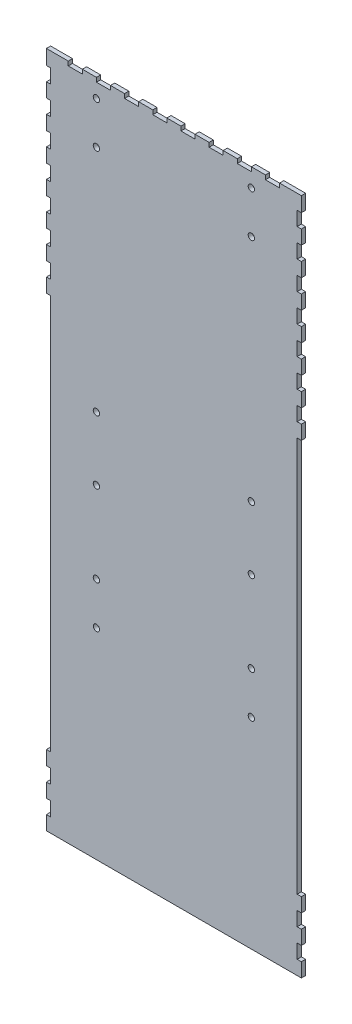
SolidWorks part; units mm, degrees
ref_plane "Front Plane" through (0, 0, 0) normal (0, 0, 1) x (1, 0, 0)
ref_plane "Top Plane" through (0, 0, 0) normal (0, 1, 0) x (1, 0, 0)
ref_plane "Right Plane" through (0, 0, 0) normal (1, 0, 0) x (0, 0, -1)
sketch "Sketch1" plane through (0, 0, 0) normal (0, 0, 1) x (1, 0, 0)
  line L2 (3, 408) -> (-12.5, 408)
  line L3 (-178, 408) -> (-178, 397.5)
  line L4 (-175, 0) -> (0, 0)
  line L5 (0, 0) -> (0, 405)
  line L6 (0, 405) -> (-175, 405)
  line L7 (-175, 405) -> (-175, 0)
  line L8 (-175, 0) -> (0, 0) construction
  line L10 (0, 405) -> (-175, 405) construction
  line L11 (-175, 405) -> (-175, 0) construction
  line L12 (-178, 397.5) -> (-175, 397.5)
  line L13 (-175, 397.5) -> (-175, 387.5)
  line L14 (-175, 387.5) -> (-178, 387.5)
  line L15 (-178, 387.5) -> (-178, 377.5)
  line L16 (-178, 408) -> (-178, -3) construction
  line L17 (-87.5, 408) -> (-87.5, -3) construction
  line L18 (-178, 377.5) -> (-175, 377.5)
  line L19 (-175, 377.5) -> (-175, 367.5)
  line L20 (-175, 367.5) -> (-178, 367.5)
  line L21 (-178, 357.5) -> (-175, 357.5)
  line L22 (-175, 357.5) -> (-175, 347.5)
  line L23 (-175, 347.5) -> (-178, 347.5)
  line L24 (-178, 337.5) -> (-175, 337.5)
  line L25 (-175, 337.5) -> (-175, 327.5)
  line L26 (-175, 327.5) -> (-178, 327.5)
  line L27 (-178, 317.5) -> (-175, 317.5)
  line L28 (-175, 317.5) -> (-175, 307.5)
  line L29 (-175, 307.5) -> (-178, 307.5)
  line L30 (-178, 297.5) -> (-175, 297.5)
  line L31 (-175, 297.5) -> (-175, 287.5)
  line L32 (-175, 287.5) -> (-178, 287.5)
  line L33 (-178, 277.5) -> (-175, 277.5)
  line L34 (-175, 277.5) -> (-175, 267.5)
  line L35 (-175, 267.5) -> (-178, 267.5)
  line L75 (-178, 367.5) -> (-178, 357.5)
  line L76 (-178, 347.5) -> (-178, 337.5)
  line L77 (-178, 327.5) -> (-178, 317.5)
  line L78 (-178, 307.5) -> (-178, 297.5)
  line L79 (-178, 287.5) -> (-178, 277.5)
  line L94 (3, -3) -> (3, 408) construction
  line L95 (0, 0) -> (0, 405) construction
  line L96 (0, 405) -> (0, 0) construction
  line L111 (3, 287.5) -> (3, 277.5)
  line L112 (3, 307.5) -> (3, 297.5)
  line L113 (3, 327.5) -> (3, 317.5)
  line L114 (3, 347.5) -> (3, 337.5)
  line L115 (3, 367.5) -> (3, 357.5)
  line L155 (0, 267.5) -> (3, 267.5)
  line L156 (0, 277.5) -> (0, 267.5)
  line L157 (3, 277.5) -> (0, 277.5)
  line L158 (0, 287.5) -> (3, 287.5)
  line L159 (0, 297.5) -> (0, 287.5)
  line L160 (3, 297.5) -> (0, 297.5)
  line L161 (0, 307.5) -> (3, 307.5)
  line L162 (0, 317.5) -> (0, 307.5)
  line L163 (3, 317.5) -> (0, 317.5)
  line L164 (0, 327.5) -> (3, 327.5)
  line L165 (0, 337.5) -> (0, 327.5)
  line L166 (3, 337.5) -> (0, 337.5)
  line L167 (0, 347.5) -> (3, 347.5)
  line L168 (0, 357.5) -> (0, 347.5)
  line L169 (3, 357.5) -> (0, 357.5)
  line L170 (0, 367.5) -> (3, 367.5)
  line L171 (0, 377.5) -> (0, 367.5)
  line L172 (3, 377.5) -> (0, 377.5)
  line L173 (3, 387.5) -> (3, 377.5)
  line L174 (0, 387.5) -> (3, 387.5)
  line L175 (0, 397.5) -> (0, 387.5)
  line L176 (3, 397.5) -> (0, 397.5)
  line L177 (3, 408) -> (3, 397.5)
  line L178 (-162.5, 408) -> (-162.5, 405)
  line L179 (-162.5, 405) -> (-152.5, 405)
  line L180 (-152.5, 405) -> (-152.5, 408)
  line L181 (-162.5, 408) -> (-178, 408)
  line L182 (3, 408) -> (-178, 408) construction
  line L183 (-142.5, 408) -> (-142.5, 405)
  line L184 (-132.5, 405) -> (-132.5, 408)
  line L185 (-142.5, 405) -> (-132.5, 405)
  line L186 (-122.5, 408) -> (-122.5, 405)
  line L187 (-112.5, 405) -> (-112.5, 408)
  line L188 (-122.5, 405) -> (-112.5, 405)
  line L189 (-102.5, 408) -> (-102.5, 405)
  line L190 (-92.5, 405) -> (-92.5, 408)
  line L191 (-102.5, 405) -> (-92.5, 405)
  line L192 (-82.5, 408) -> (-82.5, 405)
  line L193 (-72.5, 405) -> (-72.5, 408)
  line L194 (-82.5, 405) -> (-72.5, 405)
  line L195 (-62.5, 408) -> (-62.5, 405)
  line L196 (-52.5, 405) -> (-52.5, 408)
  line L197 (-62.5, 405) -> (-52.5, 405)
  line L198 (-42.5, 408) -> (-42.5, 405)
  line L199 (-32.5, 405) -> (-32.5, 408)
  line L200 (-42.5, 405) -> (-32.5, 405)
  line L201 (-22.5, 408) -> (-22.5, 405)
  line L202 (-12.5, 405) -> (-12.5, 408)
  line L203 (-22.5, 405) -> (-12.5, 405)
  line L204 (-142.5, 408) -> (-152.5, 408)
  line L205 (-122.5, 408) -> (-132.5, 408)
  line L206 (-102.5, 408) -> (-112.5, 408)
  line L207 (-82.5, 408) -> (-92.5, 408)
  line L208 (-62.5, 408) -> (-72.5, 408)
  line L209 (-42.5, 408) -> (-52.5, 408)
  line L210 (-22.5, 408) -> (-32.5, 408)
  line L211 (-178, 262.5) -> (-192.1885, 262.5) construction
  line L213 (-175, 247.5) -> (-178, 247.5) [skipped]
  line L214 (-178, 237.5) -> (-175, 237.5) [skipped]
  line L215 (-175, 237.5) -> (-175, 227.5) [skipped]
  line L216 (-175, 227.5) -> (-178, 227.5) [skipped]
  line L217 (-178, 217.5) -> (-175, 217.5) [skipped]
  line L218 (-175, 217.5) -> (-175, 207.5) [skipped]
  line L219 (-175, 207.5) -> (-178, 207.5) [skipped]
  line L220 (-178, 197.5) -> (-175, 197.5) [skipped]
  line L221 (-175, 197.5) -> (-175, 187.5) [skipped]
  line L222 (-175, 187.5) -> (-178, 187.5) [skipped]
  line L223 (-178, 177.5) -> (-175, 177.5) [skipped]
  line L224 (-175, 177.5) -> (-175, 167.5) [skipped]
  line L225 (-175, 167.5) -> (-178, 167.5) [skipped]
  line L226 (-178, 157.5) -> (-175, 157.5) [skipped]
  line L227 (-175, 157.5) -> (-175, 147.5) [skipped]
  line L228 (-175, 147.5) -> (-178, 147.5) [skipped]
  line L229 (-178, 137.5) -> (-175, 137.5) [skipped]
  line L230 (-175, 137.5) -> (-175, 127.5) [skipped]
  line L231 (-175, 127.5) -> (-178, 127.5) [skipped]
  line L232 (-178, 117.5) -> (-175, 117.5) [skipped]
  line L233 (-175, 117.5) -> (-175, 107.5) [skipped]
  line L234 (-175, 107.5) -> (-178, 107.5) [skipped]
  line L235 (-178, 97.5) -> (-175, 97.5) [skipped]
  line L236 (-175, 97.5) -> (-175, 87.5) [skipped]
  line L237 (-175, 87.5) -> (-178, 87.5) [skipped]
  line L238 (-178, 77.5) -> (-175, 77.5) [skipped]
  line L239 (-175, 77.5) -> (-175, 67.5) [skipped]
  line L240 (-175, 67.5) -> (-178, 67.5) [skipped]
  line L241 (-178, 57.5) -> (-175, 57.5) [skipped]
  line L242 (-175, 57.5) -> (-175, 47.5) [skipped]
  line L243 (-175, 47.5) -> (-178, 47.5) [skipped]
  line L244 (-178, 37.5) -> (-175, 37.5) [skipped]
  line L245 (-175, 37.5) -> (-175, 27.5) [skipped]
  line L246 (-175, 27.5) -> (-178, 27.5) [skipped]
  line L247 (-178, 17.5) -> (-175, 17.5) [skipped]
  line L248 (-175, 17.5) -> (-175, 7.5) [skipped]
  line L249 (-175, 7.5) -> (-178, 7.5) [skipped]
  line L250 (-175, 257.5) -> (-175, 247.5) [skipped]
  line L251 (-178, 257.5) -> (-175, 257.5) [skipped]
  line L254 (-178, -73) -> (3, -73)
  line L256 (-178, -3) -> (3, -3) construction
  line L257 (-178, -3) -> (3, -3) construction
  line L258 (-178, 267.5) -> (-178, 257.5)
  line L259 (-178, 257.5) -> (-175, 257.5)
  line L260 (3, 267.5) -> (3, 257.5)
  line L261 (3, 257.5) -> (0, 257.5)
  line L262 (-175, 257.5) -> (-175, 0)
  line L267 (0, 0) -> (0, 257.5)
  line L269 (-178, -23) -> (-175, -23)
  line L270 (-175, -23) -> (-175, 0)
  line L272 (3, -23) -> (0, -23)
  line L273 (0, -23) -> (0, 0)
  line L274 (-178, -33) -> (-175, -33)
  line L275 (-175, -33) -> (-175, -43)
  line L276 (-175, -43) -> (-178, -43)
  line L277 (-178, -43) -> (-178, -53)
  line L278 (-178, -53) -> (-175, -53)
  line L279 (-175, -53) -> (-175, -63)
  line L280 (-175, -63) -> (-178, -63)
  line L281 (-178, -33) -> (-178, -23)
  line L282 (-178, -73) -> (-178, -63)
  line L283 (3, -33) -> (0, -33)
  line L284 (0, -33) -> (0, -43)
  line L285 (0, -43) -> (3, -43)
  line L286 (3, -43) -> (3, -53)
  line L287 (3, -53) -> (0, -53)
  line L288 (0, -53) -> (0, -63)
  line L289 (0, -63) -> (3, -63)
  line L290 (3, -33) -> (3, -23)
  line L291 (3, -73) -> (3, -63)
  dimension "D3" = 10.5
  dimension "D4" = 10
  dimension "D6" = 10
  dimension "D7" = 10
  dimension "D8" = 15.5
  dimension "D10" = 10
  dimension "D11" = 481
  dimension "D12" = 10
  dimension "D13" = 50
  dimension "D14" = 50
  dimension "D15" = 3
  dimension "D16" = 3
  dimension "D17" = 3
  dimension "D18" = 10
  dimension "D19" = 10
  dimension "D20" = 10
  dimension "D21" = 10
  dimension "D22" = 10
  dimension "D23" = 10
  dimension "D24" = 10
  dimension "D25" = 10
  dimension "D26" = 10
  dimension "D27" = 10
  dimension "D28" = 10
  dimension "D1" = 0
  dimension "D2" = 3
  dimension "D5" = 20
  dimension "D9" = 8
extrude "Boss-Extrude1" add sketch "Sketch1" along normal blind 3
sketch "Sketch2" plane through (0, 0, 3) normal (0, 0, 1) x (1, 0, 0)
  line L116 (-175, 257.5) -> (-175, -23)
  line L117 (-175, -23) -> (-178, -23)
  line L118 (-178, -23) -> (-178, -33)
  line L119 (-178, -33) -> (-175, -33)
  line L120 (-175, -33) -> (-175, -43)
  line L121 (-175, -43) -> (-178, -43)
  line L122 (-178, -43) -> (-178, -53)
  line L123 (-178, -53) -> (-175, -53)
  line L124 (-175, -53) -> (-175, -63)
  line L125 (-175, -63) -> (-178, -63)
  line L126 (-178, -63) -> (-178, -73)
  line L127 (-178, -73) -> (3, -73)
  line L128 (3, -73) -> (3, -63)
  line L129 (3, -63) -> (0, -63)
  line L130 (0, -63) -> (0, -53)
  line L131 (0, -53) -> (3, -53)
  line L132 (3, -53) -> (3, -43)
  line L133 (3, -43) -> (0, -43)
  line L134 (0, -43) -> (0, -33)
  line L135 (0, -33) -> (3, -33)
  line L136 (3, -33) -> (3, -23)
  line L137 (3, -23) -> (0, -23)
  line L138 (0, -23) -> (0, 257.5)
  line L139 (0, 257.5) -> (3, 257.5)
  line L140 (3, 257.5) -> (3, 267.5)
  line L141 (3, 267.5) -> (0, 267.5)
  line L142 (0, 267.5) -> (0, 277.5)
  line L143 (0, 277.5) -> (3, 277.5)
  line L144 (3, 277.5) -> (3, 287.5)
  line L145 (3, 287.5) -> (0, 287.5)
  line L146 (0, 287.5) -> (0, 297.5)
  line L147 (0, 297.5) -> (3, 297.5)
  line L148 (3, 297.5) -> (3, 307.5)
  line L149 (3, 307.5) -> (0, 307.5)
  line L150 (0, 307.5) -> (0, 317.5)
  line L151 (0, 317.5) -> (3, 317.5)
  line L152 (3, 317.5) -> (3, 327.5)
  line L153 (3, 327.5) -> (0, 327.5)
  line L154 (0, 327.5) -> (0, 337.5)
  line L155 (0, 337.5) -> (3, 337.5)
  line L156 (3, 337.5) -> (3, 347.5)
  line L157 (3, 347.5) -> (0, 347.5)
  line L158 (0, 347.5) -> (0, 357.5)
  line L159 (0, 357.5) -> (3, 357.5)
  line L160 (3, 357.5) -> (3, 367.5)
  line L161 (3, 367.5) -> (0, 367.5)
  line L162 (0, 367.5) -> (0, 377.5)
  line L163 (0, 377.5) -> (3, 377.5)
  line L164 (3, 377.5) -> (3, 387.5)
  line L165 (3, 387.5) -> (0, 387.5)
  line L166 (0, 387.5) -> (0, 397.5)
  line L167 (0, 397.5) -> (3, 397.5)
  line L168 (3, 397.5) -> (3, 408)
  line L169 (3, 408) -> (-12.5, 408)
  line L170 (-12.5, 408) -> (-12.5, 405)
  line L171 (-12.5, 405) -> (-22.5, 405)
  line L172 (-22.5, 405) -> (-22.5, 408)
  line L173 (-22.5, 408) -> (-32.5, 408)
  line L174 (-32.5, 408) -> (-32.5, 405)
  line L175 (-32.5, 405) -> (-42.5, 405)
  line L176 (-42.5, 405) -> (-42.5, 408)
  line L177 (-42.5, 408) -> (-52.5, 408)
  line L178 (-52.5, 408) -> (-52.5, 405)
  line L179 (-52.5, 405) -> (-62.5, 405)
  line L180 (-62.5, 405) -> (-62.5, 408)
  line L181 (-62.5, 408) -> (-72.5, 408)
  line L182 (-72.5, 408) -> (-72.5, 405)
  line L183 (-72.5, 405) -> (-82.5, 405)
  line L184 (-82.5, 405) -> (-82.5, 408)
  line L185 (-82.5, 408) -> (-92.5, 408)
  line L186 (-92.5, 408) -> (-92.5, 405)
  line L187 (-92.5, 405) -> (-102.5, 405)
  line L188 (-102.5, 405) -> (-102.5, 408)
  line L189 (-102.5, 408) -> (-112.5, 408)
  line L190 (-112.5, 408) -> (-112.5, 405)
  line L191 (-112.5, 405) -> (-122.5, 405)
  line L192 (-122.5, 405) -> (-122.5, 408)
  line L193 (-122.5, 408) -> (-132.5, 408)
  line L194 (-132.5, 408) -> (-132.5, 405)
  line L195 (-132.5, 405) -> (-142.5, 405)
  line L196 (-142.5, 405) -> (-142.5, 408)
  line L197 (-142.5, 408) -> (-152.5, 408)
  line L198 (-152.5, 408) -> (-152.5, 405)
  line L199 (-152.5, 405) -> (-162.5, 405)
  line L200 (-162.5, 405) -> (-162.5, 408)
  line L201 (-162.5, 408) -> (-178, 408)
  line L202 (-178, 408) -> (-178, 397.5)
  line L203 (-178, 397.5) -> (-175, 397.5)
  line L204 (-175, 397.5) -> (-175, 387.5)
  line L205 (-175, 387.5) -> (-178, 387.5)
  line L206 (-178, 387.5) -> (-178, 377.5)
  line L207 (-178, 377.5) -> (-175, 377.5)
  line L208 (-175, 377.5) -> (-175, 367.5)
  line L209 (-175, 367.5) -> (-178, 367.5)
  line L210 (-178, 367.5) -> (-178, 357.5)
  line L211 (-178, 357.5) -> (-175, 357.5)
  line L212 (-175, 357.5) -> (-175, 347.5)
  line L213 (-175, 347.5) -> (-178, 347.5)
  line L214 (-178, 347.5) -> (-178, 337.5)
  line L215 (-178, 337.5) -> (-175, 337.5)
  line L216 (-175, 337.5) -> (-175, 327.5)
  line L217 (-175, 327.5) -> (-178, 327.5)
  line L218 (-178, 327.5) -> (-178, 317.5)
  line L219 (-178, 317.5) -> (-175, 317.5)
  line L220 (-175, 317.5) -> (-175, 307.5)
  line L221 (-175, 307.5) -> (-178, 307.5)
  line L222 (-178, 307.5) -> (-178, 297.5)
  line L223 (-178, 297.5) -> (-175, 297.5)
  line L224 (-175, 297.5) -> (-175, 287.5)
  line L225 (-175, 287.5) -> (-178, 287.5)
  line L226 (-178, 287.5) -> (-178, 277.5)
  line L227 (-178, 277.5) -> (-175, 277.5)
  line L228 (-175, 277.5) -> (-175, 267.5)
  line L229 (-175, 267.5) -> (-178, 267.5)
  line L230 (-178, 267.5) -> (-178, 257.5)
  line L231 (-178, 257.5) -> (-175, 257.5)
  line L232 (-175, 257.5) -> (-175, -23)
  line L233 (-175, -23) -> (-178, -23)
  line L234 (-178, -23) -> (-178, -33)
  line L235 (-178, -33) -> (-175, -33)
  line L236 (-175, -33) -> (-175, -43)
  line L237 (-175, -43) -> (-178, -43)
  line L238 (-178, -43) -> (-178, -53)
  line L239 (-178, -53) -> (-175, -53)
  line L240 (-175, -53) -> (-175, -63)
  line L241 (-175, -63) -> (-178, -63)
  line L242 (-178, -63) -> (-178, -73)
  line L243 (-178, -73) -> (3, -73)
  line L244 (3, -73) -> (3, -63)
  line L245 (3, -63) -> (0, -63)
  line L246 (0, -63) -> (0, -53)
  line L247 (0, -53) -> (3, -53)
  line L248 (3, -53) -> (3, -43)
  line L249 (3, -43) -> (0, -43)
  line L250 (0, -43) -> (0, -33)
  line L251 (0, -33) -> (3, -33)
  line L252 (3, -33) -> (3, -23)
  line L253 (3, -23) -> (0, -23)
  line L254 (0, -23) -> (0, 257.5)
  line L255 (0, 257.5) -> (3, 257.5)
  line L256 (3, 257.5) -> (3, 267.5)
  line L257 (3, 267.5) -> (0, 267.5)
  line L258 (0, 267.5) -> (0, 277.5)
  line L259 (0, 277.5) -> (3, 277.5)
  line L260 (3, 277.5) -> (3, 287.5)
  line L261 (3, 287.5) -> (0, 287.5)
  line L262 (0, 287.5) -> (0, 297.5)
  line L263 (0, 297.5) -> (3, 297.5)
  line L264 (3, 297.5) -> (3, 307.5)
  line L265 (3, 307.5) -> (0, 307.5)
  line L266 (0, 307.5) -> (0, 317.5)
  line L267 (0, 317.5) -> (3, 317.5)
  line L268 (3, 317.5) -> (3, 327.5)
  line L269 (3, 327.5) -> (0, 327.5)
  line L270 (0, 327.5) -> (0, 337.5)
  line L271 (0, 337.5) -> (3, 337.5)
  line L272 (3, 337.5) -> (3, 347.5)
  line L273 (3, 347.5) -> (0, 347.5)
  line L274 (0, 347.5) -> (0, 357.5)
  line L275 (0, 357.5) -> (3, 357.5)
  line L276 (3, 357.5) -> (3, 367.5)
  line L277 (3, 367.5) -> (0, 367.5)
  line L278 (0, 367.5) -> (0, 377.5)
  line L279 (0, 377.5) -> (3, 377.5)
  line L280 (3, 377.5) -> (3, 387.5)
  line L281 (3, 387.5) -> (0, 387.5)
  line L282 (0, 387.5) -> (0, 397.5)
  line L283 (0, 397.5) -> (3, 397.5)
  line L284 (3, 397.5) -> (3, 408)
  line L285 (3, 408) -> (-12.5, 408)
  line L286 (-12.5, 408) -> (-12.5, 405)
  line L287 (-12.5, 405) -> (-22.5, 405)
  line L288 (-22.5, 405) -> (-22.5, 408)
  line L289 (-22.5, 408) -> (-32.5, 408)
  line L290 (-32.5, 408) -> (-32.5, 405)
  line L291 (-32.5, 405) -> (-42.5, 405)
  line L292 (-42.5, 405) -> (-42.5, 408)
  line L293 (-42.5, 408) -> (-52.5, 408)
  line L294 (-52.5, 408) -> (-52.5, 405)
  line L295 (-52.5, 405) -> (-62.5, 405)
  line L296 (-62.5, 405) -> (-62.5, 408)
  line L297 (-62.5, 408) -> (-72.5, 408)
  line L298 (-72.5, 408) -> (-72.5, 405)
  line L299 (-72.5, 405) -> (-82.5, 405)
  line L300 (-82.5, 405) -> (-82.5, 408)
  line L301 (-82.5, 408) -> (-92.5, 408)
  line L302 (-92.5, 408) -> (-92.5, 405)
  line L303 (-92.5, 405) -> (-102.5, 405)
  line L304 (-102.5, 405) -> (-102.5, 408)
  line L305 (-102.5, 408) -> (-112.5, 408)
  line L306 (-112.5, 408) -> (-112.5, 405)
  line L307 (-112.5, 405) -> (-122.5, 405)
  line L308 (-122.5, 405) -> (-122.5, 408)
  line L309 (-122.5, 408) -> (-132.5, 408)
  line L310 (-132.5, 408) -> (-132.5, 405)
  line L311 (-132.5, 405) -> (-142.5, 405)
  line L312 (-142.5, 405) -> (-142.5, 408)
  line L313 (-142.5, 408) -> (-152.5, 408)
  line L314 (-152.5, 408) -> (-152.5, 405)
  line L315 (-152.5, 405) -> (-162.5, 405)
  line L316 (-162.5, 405) -> (-162.5, 408)
  line L317 (-162.5, 408) -> (-178, 408)
  line L318 (-178, 408) -> (-178, 397.5)
  line L319 (-178, 397.5) -> (-175, 397.5)
  line L320 (-175, 397.5) -> (-175, 387.5)
  line L321 (-175, 387.5) -> (-178, 387.5)
  line L322 (-178, 387.5) -> (-178, 377.5)
  line L323 (-178, 377.5) -> (-175, 377.5)
  line L324 (-175, 377.5) -> (-175, 367.5)
  line L325 (-175, 367.5) -> (-178, 367.5)
  line L326 (-178, 367.5) -> (-178, 357.5)
  line L327 (-178, 357.5) -> (-175, 357.5)
  line L328 (-175, 357.5) -> (-175, 347.5)
  line L329 (-175, 347.5) -> (-178, 347.5)
  line L330 (-178, 347.5) -> (-178, 337.5)
  line L331 (-178, 337.5) -> (-175, 337.5)
  line L332 (-175, 337.5) -> (-175, 327.5)
  line L333 (-175, 327.5) -> (-178, 327.5)
  line L334 (-178, 327.5) -> (-178, 317.5)
  line L335 (-178, 317.5) -> (-175, 317.5)
  line L336 (-175, 317.5) -> (-175, 307.5)
  line L337 (-175, 307.5) -> (-178, 307.5)
  line L338 (-178, 307.5) -> (-178, 297.5)
  line L339 (-178, 297.5) -> (-175, 297.5)
  line L340 (-175, 297.5) -> (-175, 287.5)
  line L341 (-175, 287.5) -> (-178, 287.5)
  line L342 (-178, 287.5) -> (-178, 277.5)
  line L343 (-178, 277.5) -> (-175, 277.5)
  line L344 (-175, 277.5) -> (-175, 267.5)
  line L345 (-175, 267.5) -> (-178, 267.5)
  line L346 (-178, 267.5) -> (-178, 257.5)
  line L347 (-178, 257.5) -> (-175, 257.5)
  dimension "D1" = 0
sketch "Sketch3" plane through (0, 0, 3) normal (0, 0, 1) x (1, 0, 0)
  circle A0 centre (-142.5, 365) radius 2.25 construction
  circle A1 centre (-142.5, 365) radius 2.25
  circle A2 centre (-32.5, 69.5494) radius 2.25 construction
  circle A3 centre (-32.5, 99.5494) radius 2.25 construction
  circle A4 centre (-142.5, 69.5494) radius 2.25 construction
  circle A5 centre (-142.5, 99.5494) radius 2.25 construction
  circle A6 centre (-142.5, 157.2198) radius 2.25 construction
  circle A7 centre (-32.5, 157.2198) radius 2.25 construction
  circle A8 centre (-32.5, 202.2198) radius 2.25 construction
  circle A9 centre (-142.5, 202.2198) radius 2.25 construction
  circle A10 centre (-32.5, 365) radius 2.25 construction
  circle A11 centre (-32.5, 395) radius 2.25 construction
  circle A12 centre (-142.5, 395) radius 2.25 construction
  circle A13 centre (-32.5, 69.5494) radius 2.25
  circle A14 centre (-32.5, 99.5494) radius 2.25
  circle A15 centre (-142.5, 69.5494) radius 2.25
  circle A16 centre (-142.5, 99.5494) radius 2.25
  circle A17 centre (-142.5, 157.2198) radius 2.25
  circle A18 centre (-32.5, 157.2198) radius 2.25
  circle A19 centre (-32.5, 202.2198) radius 2.25
  circle A20 centre (-142.5, 202.2198) radius 2.25
  circle A21 centre (-32.5, 365) radius 2.25
  circle A22 centre (-32.5, 395) radius 2.25
  circle A23 centre (-142.5, 395) radius 2.25
extrude "Cut-Extrude1" cut sketch "Sketch3" against normal blind 10
